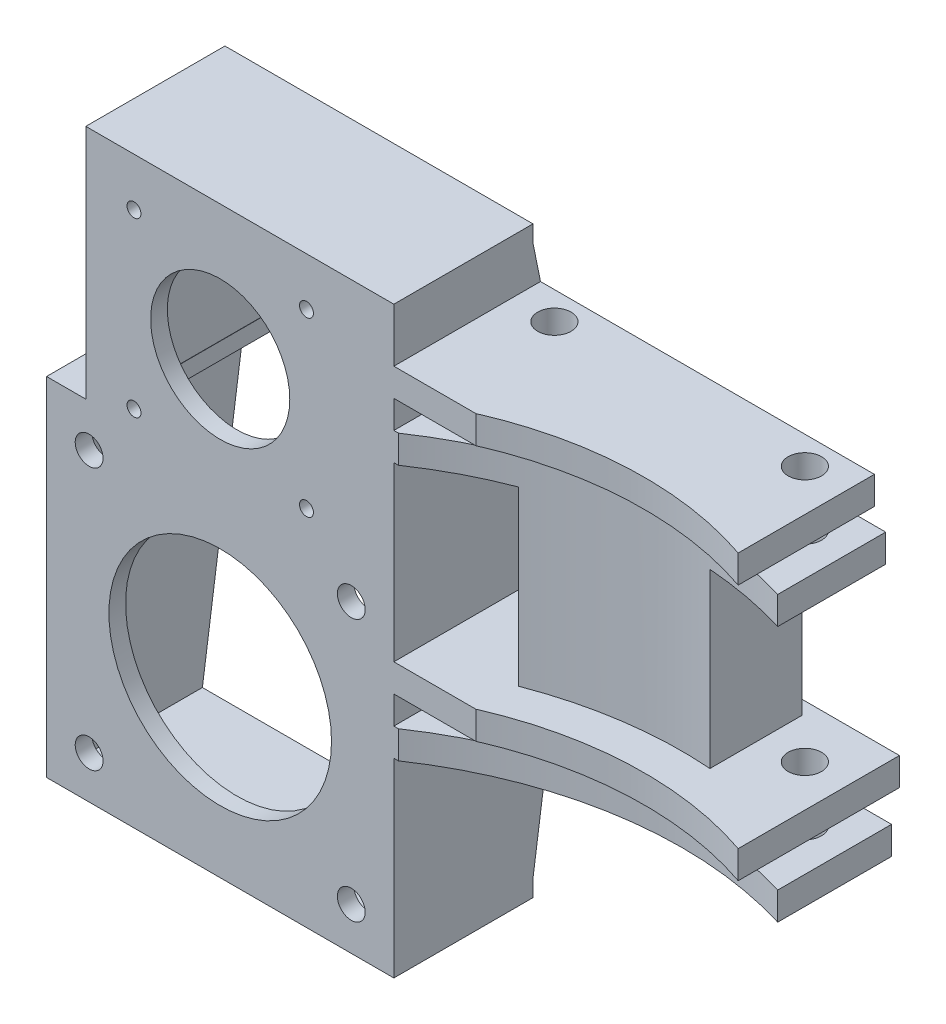
SolidWorks part; units mm, degrees
note: The reader was unsure of these and kept them because the rebuilt part matched: shared geometry of "Sketch9<2>".
ref_plane "Front Plane" through (0, 0, 0) normal (0, 0, 1) x (1, 0, 0)
ref_plane "Top Plane" through (0, 0, 0) normal (0, 1, 0) x (1, 0, 0)
ref_plane "Right Plane" through (0, 0, 0) normal (1, 0, 0) x (0, 0, -1)
sketch "Sketch1" plane through (0, 0, 0) normal (0, 0, 1) x (1, 0, 0)
  line L0 (-28.2, -28.2) -> (28.2, 28.2) construction
  line L1 (-28.2, -28.2) -> (28.2, -28.2)
  line L2 (-28.2, -28.2) -> (-28.2, 28.2)
  line L3 (-28.2, 28.2) -> (28.2, 28.2)
  line L4 (28.2, -28.2) -> (28.2, 28.2)
  line L5 (11.95, -28.2) -> (-25.7, -28.2) construction
  line L6 (-28.2, -25.7) -> (-28.2, -20.45) construction
  line L7 (16.15, 70.65) -> (-16.15, 70.65) construction
  line L8 (-21.15, 70.65) -> (21.15, 70.65)
  line L9 (-21.15, 70.65) -> (-21.15, 28.2)
  line L10 (-21.15, 28.2) -> (21.15, 28.2)
  line L11 (21.15, 70.65) -> (21.15, 28.2)
  line L12 (-21.15, 65.65) -> (-21.15, 33.35) construction
  line L13 (21.15, 33.35) -> (21.15, 65.65) construction
  line L15 (-15.49, 64.99) -> (15.5, 64.99) construction
  line L16 (-15.49, 64.99) -> (-15.49, 34) construction
  line L17 (-15.49, 34) -> (15.5, 34) construction
  line L18 (15.5, 64.99) -> (15.5, 34) construction
  circle A0 centre (-23.55, -23.55) radius 2.5
  circle A1 centre (-23.55, 23.55) radius 2.5
  circle A2 centre (23.55, 23.55) radius 2.5
  circle A3 centre (23.55, -23.55) radius 2.5
  circle A4 centre (-23.55, -23.55) radius 2.5 construction
  circle A5 centre (0, 0) radius 20
  circle A6 centre (-15.49, 34) radius 1.25
  circle A7 centre (-15.49, 64.99) radius 1.25
  circle A8 centre (15.5, 64.99) radius 1.25
  circle A9 centre (15.5, 34) radius 1.25
  circle A10 centre (0, 49.5) radius 12.5
  circle A11 centre (-15.49, 34) radius 1.25 construction
  circle A12 centre (0, 49.5) radius 13.8082 construction
  point P4 (0, 0)
  dimension "D1" = 40
  dimension "D2" = 2.5
  dimension "D3" = 25
extrude "Boss-Extrude1" add sketch "Sketch1" along normal blind 3 contours L11 L8 L9 L3 A9 A8 A7 A6 | A2 | A1 | A0 | A3 | A5
sketch "Sketch2" plane through (-28.2, 0, 0) normal (-1, 0, 0) x (0, 0, 1)
  line L0 (-22, -28.2) -> (-30, 28.2)
  line L1 (-30, 28.2) -> (0, 28.2)
  line L2 (-64, 28.2) -> (-10, 28.2) construction
  line L4 (3, -28.2) -> (-22, -28.2)
  line L5 (3, -28.2) -> (3, 28.2)
  line L6 (3, 28.2) -> (0, 28.2)
  dimension "D1" = 30
  dimension "D2" = 25
extrude "Boss-Extrude2" add sketch "Sketch2" along normal blind 3
mirror "Mirror1" about plane through (0, 0, 0) normal (1, 0, 0) of "Boss-Extrude2"
sketch "Sketch3" plane through (0, 28.2, 0) normal (0, 1, 0) x (1, 0, 0)
  line L0 (-23.55, 25) -> (23.55, 25) construction
  line L1 (-31.2, 30) -> (31.2, 30)
  line L2 (-31.2, 30) -> (-31.2, -3)
  line L3 (-31.2, -3) -> (31.2, -3)
  line L4 (31.2, 30) -> (31.2, -3)
  line L5 (23.55, 25) -> (31.2, 30) construction
  line L6 (-23.55, 25) -> (-31.2, 30) construction
  line L7 (-21.05, 0.5) -> (-26.05, 3.7) construction
  line L9 (21.1, 14) -> (21.1, 34) construction
  line L10 (-21.1, 30) -> (21.1, 30)
  line L11 (-21.1, 30) -> (-21.1, 0)
  line L12 (-21.1, 0) -> (21.1, 0)
  line L13 (21.1, 30) -> (21.1, 0)
  line L14 (-21.1, 14) -> (-21.1, 34) construction
  line L15 (-21.15, 0) -> (21.15, 0) construction
  point P10 (-23.55, 2.1)
  dimension "D2" = 5
extrude "Boss-Extrude3" add sketch "Sketch3" along normal blind 3
sketch "Sketch4" plane through (21.15, 0, 0) normal (1, 0, 0) x (0, 0, -1)
  line L0 (30, 31.2) -> (22, 70.65)
  line L1 (22, 70.65) -> (-3, 70.65)
  line L2 (-3, 70.65) -> (-3, 31.2)
  line L3 (-3, 31.2) -> (30, 31.2)
  dimension "D1" = 25
extrude "Boss-Extrude4" add sketch "Sketch4" along normal blind 3
mirror "Mirror2" about plane through (0, 0, 0) normal (1, 0, 0) of "Boss-Extrude4"
sketch "Sketch5" plane through (24.15, 0, 0) normal (1, 0, 0) x (0, 0, -1)
  line L4 (-3, 31.2) -> (30, 31.2)
  line L5 (30, 31.2) -> (22, 70.65)
  line L6 (22, 70.65) -> (-3, 70.65)
  line L7 (-3, 70.65) -> (-3, 31.2)
  line L8 (-3, 31.2) -> (30, 31.2)
  line L9 (30, 31.2) -> (22, 70.65)
  line L10 (22, 70.65) -> (-3, 70.65)
  line L11 (-3, 70.65) -> (-3, 31.2)
  dimension "D1" = 0
extrude "Boss-Extrude5" add sketch "Sketch5" along normal up to surface (7.05 mm away)
sketch "Sketch6" plane through (0, -28.2, 0) normal (0, -1, 0) x (1, 0, 0)
  line L1 (-31.2, 3) -> (31.2, 3)
  line L2 (-31.2, 3) -> (-31.2, -22)
  line L3 (-31.2, -22) -> (31.2, -22)
  line L4 (31.2, 3) -> (31.2, -22)
extrude "Boss-Extrude6" add sketch "Sketch6" along normal blind 3
sketch "Sketch7" plane through (0, 70.65, 0) normal (0, 1, 0) x (1, 0, 0)
  line L1 (31.2, 22) -> (-24.15, 22)
  line L2 (31.2, 22) -> (31.2, -3)
  line L3 (31.2, -3) -> (-24.15, -3)
  line L4 (-24.15, 22) -> (-24.15, -3)
extrude "Boss-Extrude7" add sketch "Sketch7" along normal blind 3
sketch "Sketch8" plane through (31.2, 0, 0) normal (1, 0, 0) x (0, 0, -1)
  line L0 (-15.0148, 59) -> (-2.6246, 59) construction
  line L1 (-3, 64) -> (23.3485, 64)
  line L2 (-3, 64) -> (-3, 59)
  line L3 (-3, 59) -> (23.3485, 59)
  line L4 (23.3485, 64) -> (23.3485, 59)
  line L5 (25.3764, 54) -> (-3, 54)
  line L6 (25.3764, 54) -> (25.3764, 49)
  line L7 (25.3764, 49) -> (-3, 49)
  line L8 (-3, 54) -> (-3, 49)
  line L9 (27.844, 13) -> (-3, 13)
  line L10 (27.844, 13) -> (27.844, 18)
  line L11 (27.844, 18) -> (-3, 18)
  line L12 (-3, 13) -> (-3, 18)
  line L13 (26.4255, 8) -> (-3, 8)
  line L14 (26.4255, 8) -> (26.4255, 3)
  line L15 (26.4255, 3) -> (-3, 3)
  line L16 (-3, 8) -> (-3, 3)
  line L17 (-3, -31.2) -> (-3, 73.65) construction
  line L18 (22, 70.65) -> (30, 31.2) construction
  line L19 (-8.1101, 54) -> (-3.1101, 54) construction
  line L20 (-10.5345, 13) -> (-104.0412, 13) construction
  line L21 (-8.1101, 8) -> (-3.1101, 8) construction
  line L22 (30, 28.2) -> (22, -28.2) construction
  dimension "D1" = 5
  dimension "D2" = 5
  dimension "D3" = 5
  dimension "D4" = 5
extrude "Boss-Extrude8" add sketch "Sketch8" along normal blind 60
sketch "Sketch9" plane through (0, 54, 0) normal (0, 1, 0) x (1, 0, 0)
  circle A0 centre (70.9709, -60.2646) radius 69.2527
  circle A2 centre (70.9709, -60.2646) radius 19.2527
  arc A3 (90.6211, 4.0533) -> (89.6795, 4.3335) centre (70.9709, -60.2646) ccw construction
  dimension "D1" = 2
  dimension "D2" = 50
extrude "Cut-Extrude1" cut sketch "Sketch9" against normal up to surface (5 mm away) up to face at (61.2, 49, -11.1882)
extrude "Cut-Extrude2" cut sketch "Sketch9<2>" along normal up to surface (5 mm away) from surface
sketch "Sketch9<2>" plane through (0, 54, 0) normal (0, 1, 0) x (1, 0, 0) same geometry as "Sketch9"
sketch "Sketch10" plane through (0, 64, 0) normal (0, 1, 0) x (1, 0, 0)
  circle A0 centre (70.9709, -60.2646) radius 62.5
  arc A1 (33.1137, -10.5345) -> (26.363, -104.0412) centre (70.9709, -60.2646) ccw construction
extrude "Cut-Extrude3" cut sketch "Sketch10" against normal through all both and the other way through all
sketch "Sketch11" plane through (0, 49, 0) normal (0, -1, 0) x (1, 0, 0)
  line L0 (91.2, -25.3764) -> (31.2, -25.3764) construction
  line L1 (46.2, -25.3764) -> (76.2, -25.3764)
  line L2 (46.2, -25.3764) -> (46.2, -4.4064)
  line L4 (76.2, -25.3764) -> (76.2, -8.7904)
  line L5 (31.2, 3) -> (31.2, -25.3764) construction
  line L6 (91.2, -5.9677) -> (91.2, -25.3764) construction
  arc A0 (32.026, 3) -> (91.2, -5.9677) centre (70.9709, 60.2646) ccw construction
  arc A1 (46.2, -4.4064) -> (76.2, -8.7904) centre (70.9709, 60.2646) ccw
  dimension "D1" = 15
  dimension "D2" = 15
extrude "Boss-Extrude9" add sketch "Sketch11" along normal up to surface (31 mm away) up to face at (58.111, 18, -10.5611)
sketch "Sketch12" plane through (0, 54, 0) normal (0, 1, 0) x (1, 0, 0)
  line L0 (76.2, 23.3485) -> (76.2, 2.0163) construction
  line L1 (91.2, 23.3485) -> (31.2, 23.3485) construction
  line L2 (91.2, 23.3485) -> (91.2, -1.1289) construction
  line L3 (76.2, 23.3485) -> (91.2, 23.3485) construction
  line L4 (31.2, 23.3485) -> (31.2, -3) construction
  circle A0 centre (83.7, 18.3485) radius 3
  arc A1 (91.2, -1.1289) -> (45.9306, -3) centre (70.9709, -60.2646) ccw construction
  circle A2 centre (38.7, 18.3485) radius 3
  point P11 (83.7, 23.3485)
  dimension "D2" = 6
  dimension "D1" = 15
  dimension "D3" = 5
  dimension "D4" = 7.5
  dimension "D5" = 5
extrude "Cut-Extrude4" cut sketch "Sketch12" against normal through all both and the other way through all
